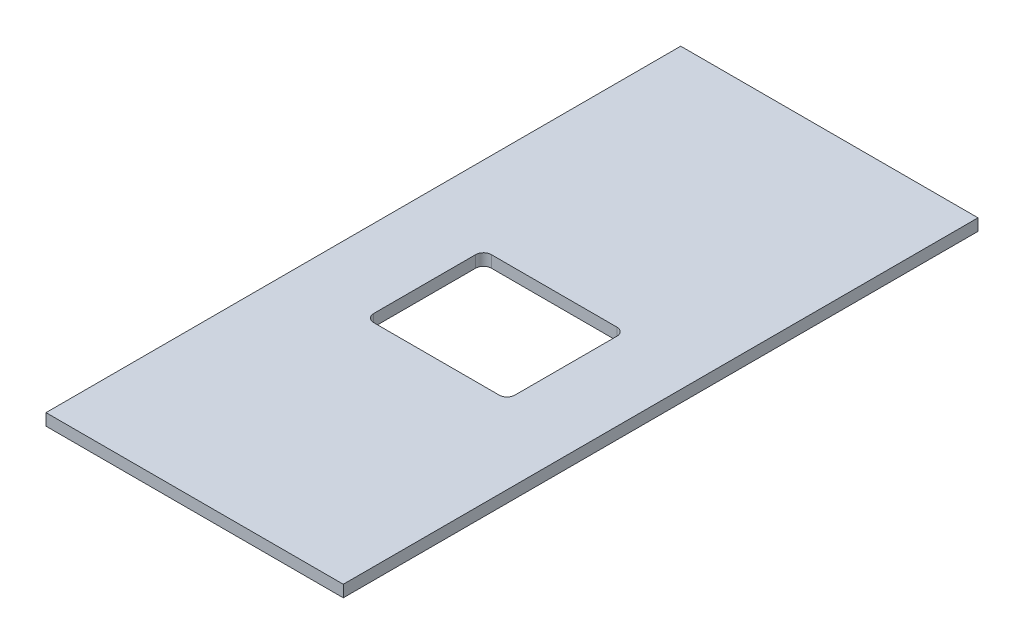
SolidWorks part; units mm, degrees
material "Balsa"
ref_plane "Front Plane" through (0, 0, 0) normal (0, 0, 1) x (1, 0, 0)
ref_plane "Top Plane" through (0, 0, 0) normal (0, 1, 0) x (1, 0, 0)
ref_plane "Right Plane" through (0, 0, 0) normal (1, 0, 0) x (0, 0, -1)
sketch "Sketch1" plane through (0, 0, 0) normal (0, 1, 0) x (1, 0, 0)
  line L0 (-152.4, 304.8) -> (152.4, 304.8) construction
  line L1 (152.4, 304.8) -> (152.4, -304.8) construction
  line L2 (0, 304.8) -> (0, 0) construction
  line L3 (0, 0) -> (152.4, 0) construction
  dimension "Width" = 304.8
  dimension "Length" = 609.6
sketch "Sketch2" plane through (0, 0, 0) normal (1, 0, 0) x (0, 0, -1)
  line L0 (304.8, 0) -> (304.8, -9.525) construction
  dimension "Thk" = 9.525
sketch "Sketch3" plane through (0, 0, 0) normal (0, 1, 0) x (1, 0, 0)
  line L1 (-152.4, 304.8) -> (152.4, 304.8)
  line L2 (-152.4, 304.8) -> (-152.4, -304.8)
  line L3 (-152.4, -304.8) -> (152.4, -304.8)
  line L4 (152.4, 304.8) -> (152.4, -304.8)
extrude "Boss-Extrude1" add sketch "Sketch3" against normal up to vertex (9.525 mm away) up to point (0, -9.525, -304.8)
sketch "Sketch4" plane through (0, 0, 0) normal (0, 1, 0) x (1, 0, 0)
  line L0 (152.4, -304.8) -> (152.4, 304.8) construction
  line L1 (-152.4, 304.8) -> (152.4, 304.8)
  line L2 (-152.4, 304.8) -> (-152.4, 208.661)
  line L3 (-120.245, 208.661) -> (120.245, 208.661)
  line L4 (152.4, 304.8) -> (152.4, 208.661)
  line L5 (-152.4, -304.8) -> (152.4, -304.8) construction
  line L6 (0, 0) -> (0, 208.661) construction
  line L8 (-152.4, 208.661) -> (-152.4, -304.8)
  line L9 (-152.4, -304.8) -> (-120.245, -304.8)
  line L10 (-120.245, 208.661) -> (-120.245, -304.8)
  line L11 (152.4, 208.661) -> (152.4, -304.8)
  line L12 (120.245, 208.661) -> (120.245, -304.8)
  line L13 (152.4, -304.8) -> (120.245, -304.8)
  dimension "D1" = 513.461
  dimension "D2" = 32.155
  dimension "D3" = 32.155
extrude "Cut-Extrude1" cut sketch "Sketch4" against normal blind 15.24 contours L2 L8 L9 L10 L3 L12 L13 L11 L4 L1
sketch "Sketch5" plane through (0, 0, 0) normal (0, 1, 0) x (1, 0, 0)
  line L1 (-50.8, -109.22) -> (50.8, -109.22)
  line L2 (-57.15, -102.87) -> (-57.15, -20.32)
  line L3 (-50.8, -13.97) -> (50.8, -13.97)
  line L4 (57.15, -102.87) -> (57.15, -20.32)
  line L5 (-57.15, -109.22) -> (57.15, -13.97) construction
  line L6 (-57.15, -13.97) -> (57.15, -109.22) construction
  arc A0 (-50.8, -109.22) -> (-57.15, -102.87) centre (-50.8, -102.87) cw
  arc A1 (50.8, -109.22) -> (57.15, -102.87) centre (50.8, -102.87) ccw
  arc A2 (50.8, -13.97) -> (57.15, -20.32) centre (50.8, -20.32) cw
  arc A3 (-57.15, -20.32) -> (-50.8, -13.97) centre (-50.8, -20.32) cw
  point P0 (0, -61.595)
  dimension "D4" = 6.35
  dimension "D1" = 95.25
  dimension "D2" = 61.595
  dimension "D3" = 114.3
extrude "Cut-Extrude2" cut sketch "Sketch5" against normal blind 12.7
